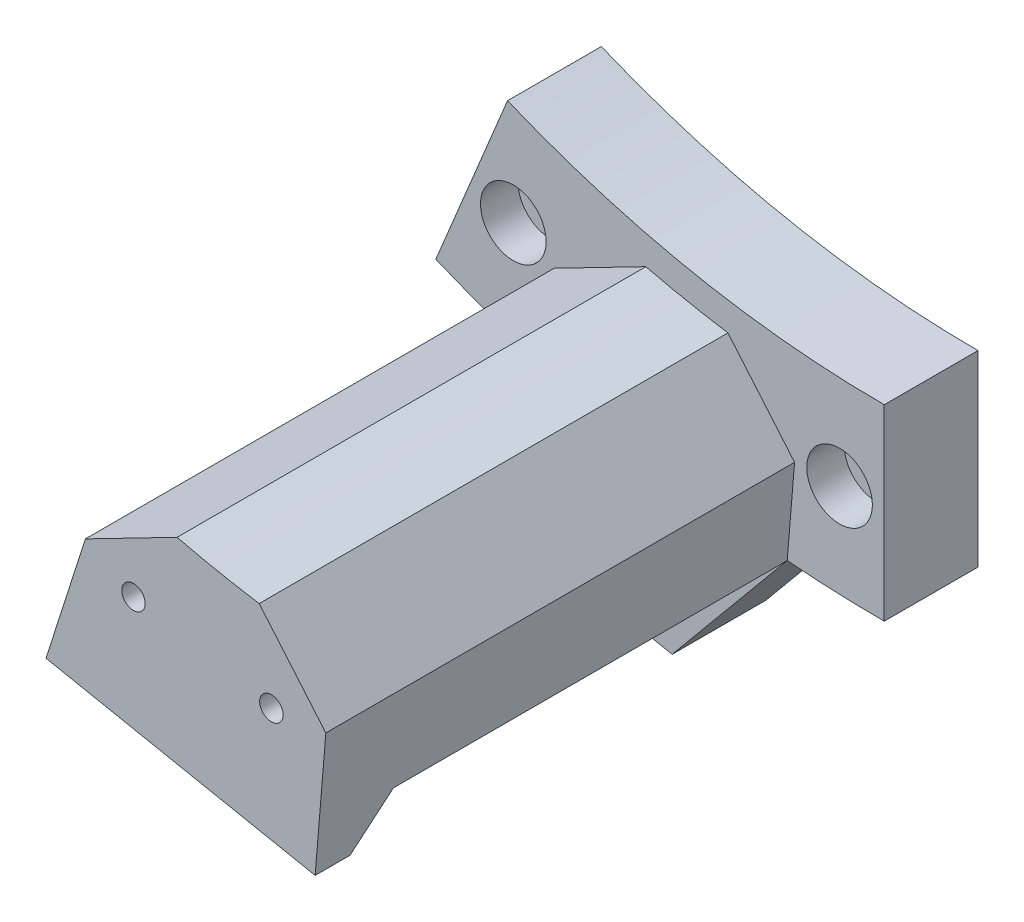
SolidWorks part; units mm, degrees
ref_plane "Plan de face" through (0, 0, 0) normal (0, 0, 1) x (1, 0, 0)
ref_plane "Plan de dessus" through (0, 0, 0) normal (0, 1, 0) x (1, 0, 0)
ref_plane "Plan de droite" through (0, 0, 0) normal (1, 0, 0) x (0, 0, -1)
sketch "Esquisse1" plane through (0, 0, 0) normal (0, 0, 1) x (1, 0, 0)
  line L0 (0, 0) -> (0, -125) construction
  line L1 (0, 0) -> (-47.8354, -115.4849) construction
  line L2 (-40.1818, -97.0074) -> (-47.8354, -115.4849)
  line L3 (0, -105) -> (0, -125)
  arc A0 (0, -125) -> (-47.8354, -115.4849) centre (0, 0) cw
  arc A1 (0, -105) -> (-40.1818, -97.0074) centre (0, 0) cw
  dimension "D2" = 125
  dimension "D3" = 105
  dimension "D1" = 22.5
extrude "Boss.-Extru.1" add sketch "Esquisse1" along normal blind 10
sketch "Esquisse2" plane through (0, 0, 10) normal (0, 0, 1) x (1, 0, 0)
  line L0 (0, 0) -> (-24.3863, -122.5982) construction
  line L1 (0, 0) -> (-10.351, -124.5707) construction
  line L2 (0, 0) -> (-38.108, -119.0495) construction
  line L3 (-32.9253, -102.8587) -> (-38.108, -119.0495)
  line L4 (-8.9433, -107.6291) -> (-10.351, -124.5707)
  arc A0 (-47.8354, -115.4849) -> (0, -125) centre (0, 0) ccw construction
  arc A1 (-10.351, -124.5707) -> (-38.108, -119.0495) centre (0, 0) cw
  arc A2 (-8.9433, -107.6291) -> (-32.9253, -102.8587) centre (0, 0) cw
  arc A3 (-40.1818, -97.0074) -> (0, -105) centre (0, 0) ccw construction
  point P10 (-24.3863, -122.5982)
  dimension "D1" = 3
  dimension "D2" = 13
extrude "Boss.-Extru.2" add sketch "Esquisse2" along normal blind 48
sketch "Esquisse4" plane through (0, 0, 58) normal (0, 0, 1) x (1, 0, 0)
  line L0 (-39.4132, -123.1267) -> (-10.7055, -128.837)
  line L1 (-10.7055, -128.837) -> (-8.9433, -107.6291)
  line L2 (-32.9253, -102.8587) -> (-39.4132, -123.1267)
  line L3 (-32.9253, -102.8587) -> (-38.108, -119.0495) construction
  line L4 (-10.351, -124.5707) -> (-8.9433, -107.6291) construction
  arc A0 (-32.9253, -102.8587) -> (-8.9433, -107.6291) centre (0, 0) ccw construction
  arc A1 (-32.9253, -102.8587) -> (-8.9433, -107.6291) centre (0, 0) ccw
  arc A2 (-38.108, -119.0495) -> (-10.351, -124.5707) centre (0, 0) ccw construction
  point P14 (-24.3863, -122.5982)
  dimension "D1" = 3.45
extrude "Boss.-Extru.3" add sketch "Esquisse4" along normal blind 2
chamfer "Chanfrein1" distance 6 angle 45 1 edges at (-24.3863, -122.5982, 58)
sketch "Esquisse5" plane through (0, 0, 10) normal (0, 0, 1) x (1, 0, 0)
  line L0 (0, 0) -> (-43.0087, -117.368) construction
  line L1 (0, 0) -> (-5.18, -124.8926) construction
  line L2 (-43.0087, -117.368) -> (-36.1273, -98.5891) construction
  line L3 (0, -125) -> (0, -105) construction
  line L4 (-40.1818, -97.0074) -> (-47.8354, -115.4849) construction
  arc A0 (-47.8354, -115.4849) -> (-38.108, -119.0495) centre (0, 0) ccw construction
  arc A1 (-10.351, -124.5707) -> (0, -125) centre (0, 0) ccw construction
  arc A2 (-40.1818, -97.0074) -> (0, -105) centre (0, 0) ccw construction
  arc A3 (0, -115) -> (-44.0086, -106.2461) centre (0, 0) cw construction
  circle A4 centre (-4.7656, -114.9012) radius 1.75
  circle A5 centre (-39.568, -107.9786) radius 1.75
  point P20 (-39.568, -107.9786)
  dimension "D1" = 3.5
extrude "Enlèv. mat.-Extru.1" cut sketch "Esquisse5" against normal up to next
sketch "Esquisse6" plane through (0, 0, 10) normal (0, 0, 1) x (1, 0, 0)
  circle A0 centre (-39.568, -107.9786) radius 3.5
  circle A1 centre (-4.7656, -114.9012) radius 3.5
  dimension "D1" = 7
extrude "Enlèv. mat.-Extru.2" cut sketch "Esquisse6" against normal blind 4
chamfer "Chanfrein2" distance 7.5 angle 45 2 edges at (-8.9433, -107.6291, 35) (-32.9253, -102.8587, 35)
sketch "Esquisse7" plane through (0, 0, 60) normal (0, 0, 1) x (1, 0, 0)
  line L0 (-21.0698, -105.9248) -> (-24.3863, -122.5982) construction
  line L1 (-30.0839, -112.7983) -> (-15.3721, -115.7247) construction
  arc A0 (-38.108, -119.0495) -> (-10.351, -124.5707) centre (0, 0) ccw construction
  arc A1 (-38.108, -119.0495) -> (-10.351, -124.5707) centre (0, 0) ccw construction
  arc A2 (-25.4295, -104.9635) -> (-16.674, -106.7051) centre (0, 0) ccw construction
  circle A3 centre (-30.0839, -112.7983) radius 1.25
  circle A4 centre (-15.3721, -115.7247) radius 1.25
  point P12 (-22.728, -114.2615)
  point P13 (-22.728, -114.2615)
  dimension "D1" = 2.5
  dimension "D2" = 15
extrude "Enlèv. mat.-Extru.3" cut sketch "Esquisse7" against normal blind 10
sketch "Esquisse8" plane through (0, 0, 0) normal (0, 0, -1) x (-1, 0, 0)
  line L0 (24.3863, -122.5982) -> (0, 0) construction
  line L2 (24.3863, -122.5982) -> (27.5468, -138.4869) construction
  line L3 (32.4334, -137.4246) -> (38.108, -119.0495)
  line L5 (32.4334, -137.4246) -> (22.6256, -139.3755)
  line L7 (22.6256, -139.3755) -> (10.351, -124.5707)
  line L8 (35.2118, -110.0017) -> (38.108, -119.0495) construction
  line L9 (35.2118, -110.0017) -> (38.108, -119.0495) construction
  arc A1 (38.108, -119.0495) -> (10.351, -124.5707) centre (0, 0) cw
  arc A5 (0, -125) -> (47.8354, -115.4849) centre (0, 0) ccw construction
  arc M14 (0, -125) -> (47.8354, -115.4849) centre (0, 0) ccw
  dimension "D2" = 141.2
  dimension "D3" = 10
extrude "Boss.-Extru.4" add sketch "Esquisse8" against normal blind 10 contours L7 L3 M14 region at (-25.6818, -129.111, 0)
sketch "Esquisse9" plane through (-27.5295, -138.4, 0) normal (-0.1951, -0.9808, 0) x (0.9808, -0.1951, 0)
  line L0 (5, 10) -> (-5, 0) construction
  circle A0 centre (0, 5) radius 2.75
  dimension "D1" = 5.5
extrude "Enlèv. mat.-Extru.4" cut sketch "Esquisse9" against normal blind 2
